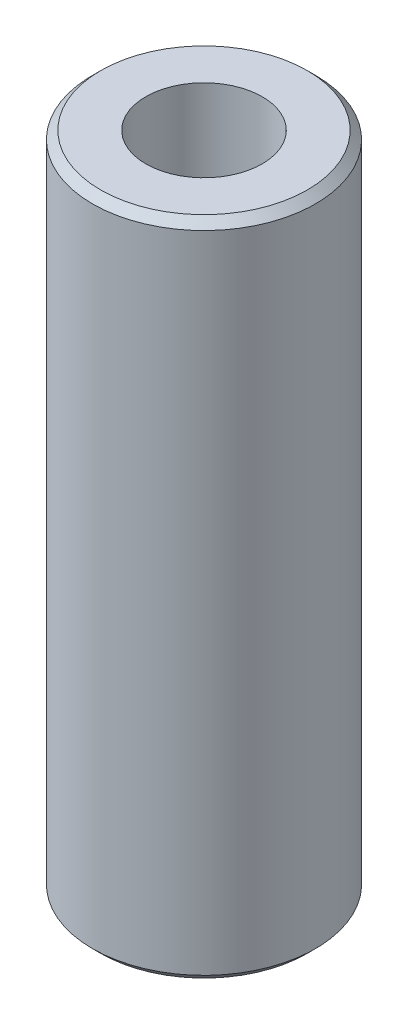
SolidWorks part; units mm, degrees
ref_plane "Front Plane" through (0, 0, 0) normal (0, 0, 1) x (1, 0, 0)
ref_plane "Top Plane" through (0, 0, 0) normal (0, 1, 0) x (1, 0, 0)
ref_plane "Right Plane" through (0, 0, 0) normal (1, 0, 0) x (0, 0, -1)
sketch "Sketch1" plane through (0, 0, 0) normal (0, 1, 0) x (1, 0, 0)
  circle A0 centre (0, 0) radius 57.5
  dimension "SHAFT_OD" = 115
extrude "Boss-Extrude1" add sketch "Sketch1" along normal blind 341.1382
sketch "Sketch2" plane through (0, 0, 0) normal (0, 1, 0) x (1, 0, 0)
  circle A0 centre (0, 0) radius 30.0369
  dimension "BORE_D" = 60.0738
extrude "Cut-Extrude1" cut sketch "Sketch2" along normal through all
chamfer "Chamfer1" distance 4.1677 angle 45 2 edges at (0, 341.1382, 57.5) (0, 0, 57.5)
